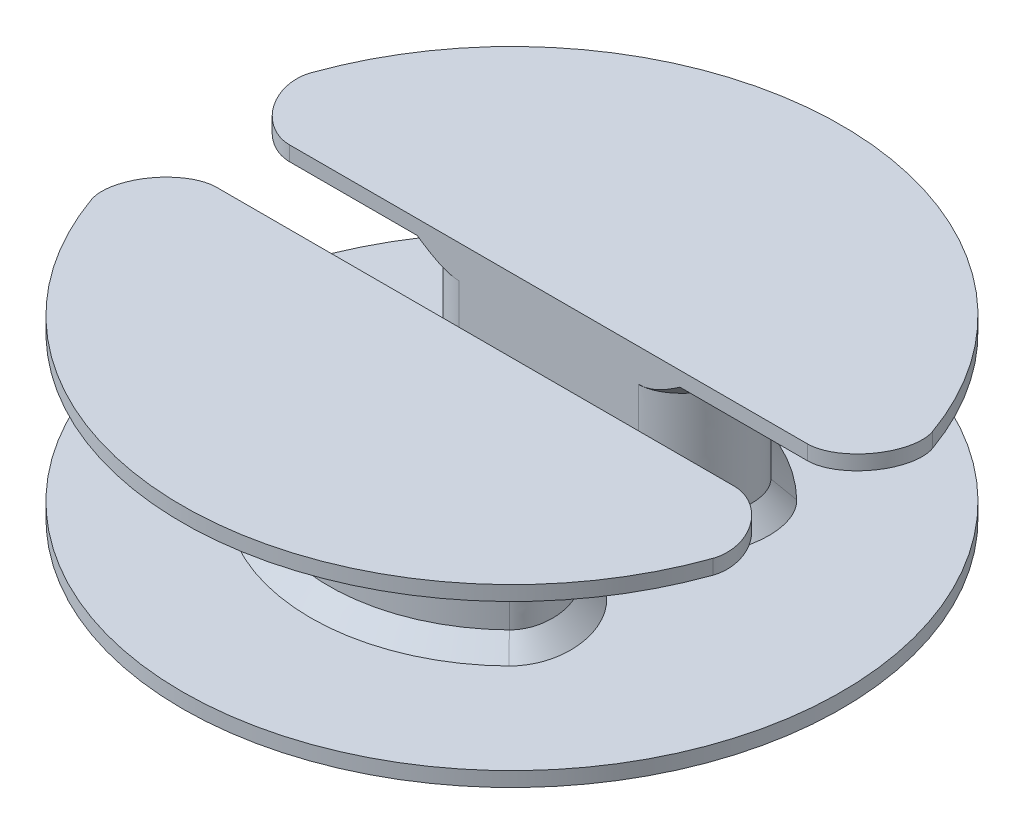
SolidWorks part; units mm, degrees
ref_plane "Front Plane" through (0, 0, 0) normal (0, 0, 1) x (1, 0, 0)
ref_plane "Top Plane" through (0, 0, 0) normal (0, 1, 0) x (1, 0, 0)
ref_plane "Right Plane" through (0, 0, 0) normal (1, 0, 0) x (0, 0, -1)
sketch "Sketch1" plane through (0, 0, 0) normal (0, 1, 0) x (1, 0, 0)
  line L0 (-90, 0) -> (90, 0)
  line L1 (-90, -10) -> (90, -10)
  line L2 (-90, 10) -> (90, 10)
  circle A0 centre (0, 0) radius 50
  circle A1 centre (0, 0) radius 90
  point P11 (0, 0)
  point P12 (0, 0)
  point P13 (0, 0)
  dimension "D3" = 100
  dimension "D1" = 10
  dimension "D2" = 10
  dimension "D4" = 40
extrude "Boss-Extrude1" add sketch "Sketch1" along normal blind 40 contours L1 A0 region at (0, 0, 26.7184)
ref_plane "Plane1" through (0, 40, 0) normal (0, 1, 0) x (1, 0, 0)
extrude "Boss-Extrude5" add sketch "Sketch1<7>" along normal blind 4 from surface contours L1 A1 A0 | L1 A0 region at (0, 0, 26.7184) region at (69.2163, 0, 11.9596) starting at plane "Plane1"
sketch "Sketch1<7>" plane through (0, 0, 0) normal (0, 1, 0) x (1, 0, 0) same geometry as "Sketch1"
fillet "Fillet2" radius 15 4 edges at (48.9898, 20, 10) (-48.9898, 20, 10) (89.4427, 42, 10) (-89.4427, 42, 10) conic radius 20
mirror "Mirror8" about plane through (0, 0, 0) normal (0, 0, 1) of bodies 109
extrude "Boss-Extrude6" add sketch "Sketch1<8>" against normal blind 4 contours A1
sketch "Sketch1<8>" plane through (0, 0, 0) normal (0, 1, 0) x (1, 0, 0) same geometry as "Sketch1"
chamfer "Chamfer1" distance 5 angle 45 12 edges
